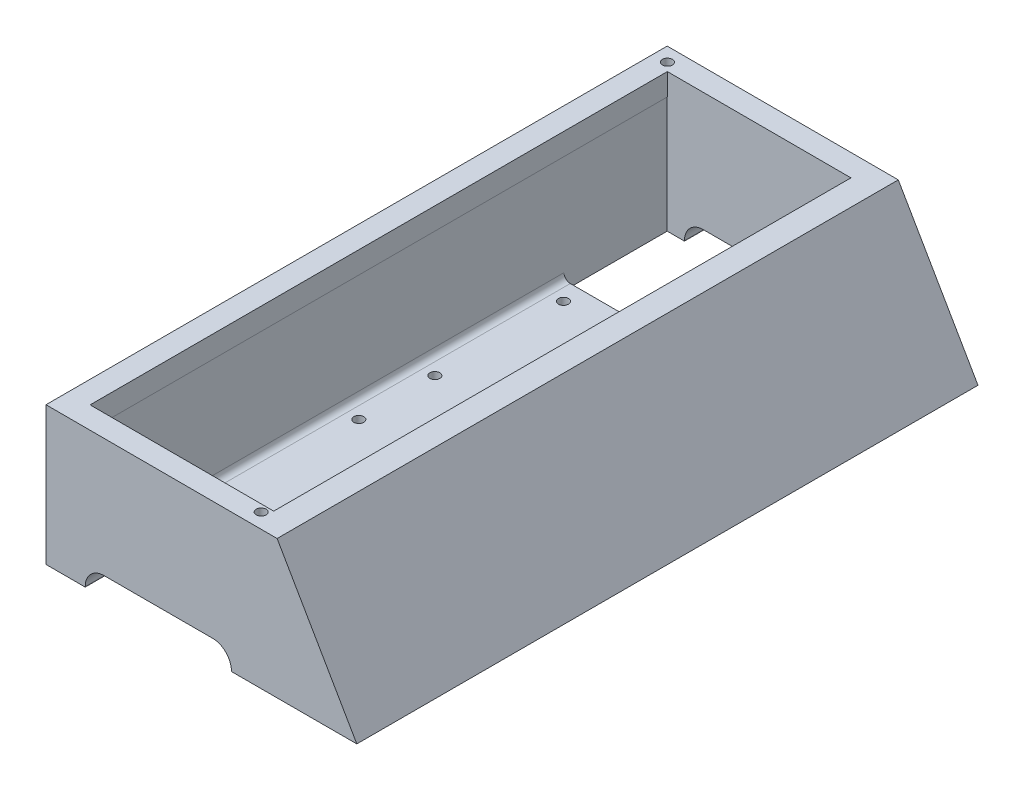
SolidWorks part; units mm, degrees
ref_plane "Alzado" through (0, 0, 0) normal (0, 0, 1) x (1, 0, 0)
ref_plane "Planta" through (0, 0, 0) normal (0, 1, 0) x (1, 0, 0)
ref_plane "Vista lateral" through (0, 0, 0) normal (1, 0, 0) x (0, 0, -1)
sketch "Sketch1" plane through (0, 0, 0) normal (0, 0, 1) x (1, 0, 0)
  line L0 (0, 0) -> (99.07, 0)
  line L1 (99.07, 0) -> (73.665, 44.0028)
  line L2 (0, 0) -> (0, 44.1)
  line L3 (0, 44.1) -> (73.665, 44.0028)
  dimension "D1" = 99.07
  dimension "D2" = 60
  dimension "D3" = 50.81
  dimension "D4" = 44.1
  dimension "D5" = 90
extrude "Boss-Extrude1" add sketch "Sketch1" along normal blind 198
shell "Shell1" thickness 7 removed face at (49.535, 0, 99)
sketch "Sketch2" plane through (68.2403, 39.3986, 0) normal (-0.866, -0.5, 0) x (0, 0, 1)
  line L0 (191, -3.5) -> (191, -45.4935) construction
  line L1 (7, -45.4935) -> (191, -45.4935)
  line L2 (7, -45.4935) -> (7, 46.3403)
  line L3 (7, 46.3403) -> (191, 46.3403)
  line L4 (191, -45.4935) -> (191, 46.3403)
  line L5 (7, -45.4935) -> (7, -2.7603) construction
  dimension "D1" = 0
  dimension "D2" = 0
extrude "Cut-Extrude1" cut sketch "Sketch2" along normal blind 10
sketch "Sketch3" plane through (0.0582, 44.0999, 0) normal (0.0013, 1, 0) x (1, -0.0013, 0)
  line L0 (7, -7) -> (90.987, -7) construction
  line L1 (7, -191) -> (58.0157, -191)
  line L2 (7, -191) -> (7, -7)
  line L3 (7, -7) -> (58.0157, -7)
  line L4 (58.0157, -191) -> (58.0157, -7)
  line L5 (7, -191) -> (90.987, -191) construction
  line L6 (7, -191) -> (7, -7) construction
  line L7 (58.0157, -7) -> (58.0157, -191) construction
  dimension "D1" = 0
  dimension "D2" = 0
  dimension "D3" = 0
  dimension "D4" = 0
extrude "Cut-Extrude3" cut sketch "Sketch3" against normal blind 10
sketch "Sketch4" plane through (0, 0, 0) normal (0, -1, 0) x (1, 0, 0)
  line L0 (7, 191) -> (7, 158.11) construction
  line L1 (7.049, 7) -> (7.049, 39.89) construction
  line L2 (90.9871, 191) -> (90.9871, 7) construction
  line L3 (7, 158.11) -> (50.2271, 158.11)
  line L4 (7, 158.11) -> (7, 39.89)
  line L5 (7, 39.89) -> (50.2271, 39.89)
  line L6 (50.2271, 158.11) -> (50.2271, 39.89)
  line L7 (7, 191) -> (90.9871, 191) construction
  line L8 (7, 7) -> (90.9871, 7) construction
  line L15 (90.9871, 81) -> (80.9871, 81)
  line L16 (90.9871, 81) -> (90.9871, 91)
  line L17 (90.9871, 91) -> (80.9871, 91)
  line L18 (80.9871, 81) -> (80.9871, 91)
  dimension "D1" = 32.89
  dimension "D2" = 32.89
  dimension "D3" = 40.76
  dimension "D4" = 32.89
  dimension "D5" = 32.89
  dimension "D8" = 10
  dimension "D10" = 0
extrude "Boss-Extrude2" add sketch "Sketch4" against normal blind 3
sketch "Sketch6" plane through (0, 3, 0) normal (0, 1, 0) x (1, 0, 0)
  circle A0 centre (12.8305, -45.8872) radius 1.585
  circle A1 centre (12.8305, -86.8872) radius 1.585
  circle A2 centre (12.8305, -111.1128) radius 1.585
  circle A3 centre (12.8305, -152.1128) radius 1.585
extrude "Cut-Extrude5" cut sketch "Sketch6" against normal blind 10
sketch "Sketch10" plane through (0, 0, 0) normal (0, -1, 0) x (1, 0, 0)
  circle A0 centre (84.0927, 85.7391) radius 1.585
extrude "Cut-Extrude8" cut sketch "Sketch10" against normal blind 5
sketch "Sketch9" plane through (0, 0, 198) normal (0, 0, 1) x (1, 0, 0)
  line L0 (0, 44.1) -> (0, 0) construction
  line L1 (12.5, 0) -> (59.0927, 0)
  line L2 (12.5, 0) -> (12.5, 6.1795)
  line L3 (12.5, 6.1795) -> (59.0927, 6.1795)
  line L4 (59.0927, 0) -> (59.0927, 6.1795)
  line L5 (71.5927, -45.1936) -> (71.5927, 0) construction
  dimension "D1" = 12.5
  dimension "D2" = 12.5
extrude "Cut-Extrude7" cut sketch "Sketch9" against normal blind 10
ref_plane "Plane1" through (0, 0, 99) normal (0, 0, -1) x (-1, 0, 0)
mirror "Mirror1" about plane through (0, 0, 99) normal (0, 0, -1) of "Cut-Extrude7"
fillet "Fillet1" radius 6 2 edges at (12.5, 6.1795, 3.5) (59.0927, 6.1795, 3.5)
fillet "Fillet2" radius 6 2 edges at (59.0927, 6.1795, 194.5) (12.5, 6.1795, 194.5)
mirror "Mirror2" about plane through (0, 0, 99) normal (0, 0, -1) of "Boss-Extrude2", "Cut-Extrude8"
sketch "Sketch11" plane through (0, 0, 0) normal (0, -1, 0) x (1, 0, 0)
  circle A0 centre (12.8305, 152.1128) radius 1.585
  circle A1 centre (12.8305, 111.1128) radius 1.585
  circle A2 centre (12.8305, 86.8872) radius 1.585
  circle A3 centre (12.8305, 45.8872) radius 1.585
extrude "Cut-Extrude9" cut sketch "Sketch11" against normal blind 5
sketch "Sketch12" plane through (0.0582, 44.0999, 0) normal (0.0013, 1, 0) x (1, -0.0013, 0)
  circle A0 centre (63.7683, -193.2457) radius 1.585
  circle A1 centre (4.417, -4.4022) radius 1.585
  dimension "D1" = 3.17
  dimension "D2" = 3.17
extrude "Cut-Extrude10" cut sketch "Sketch12" against normal blind 5
fillet "Fillet3" radius 5 4 edges at (90.1211, 1.5, 117) (90.1211, 1.5, 107) (90.1211, 1.5, 91) (90.1211, 1.5, 81)
fillet "Fillet4" radius 1 2 edges at (89.255, 3, 112) (89.255, 3, 86)
fillet "Fillet5" radius 2 1 edges at (7, 3, 99)
